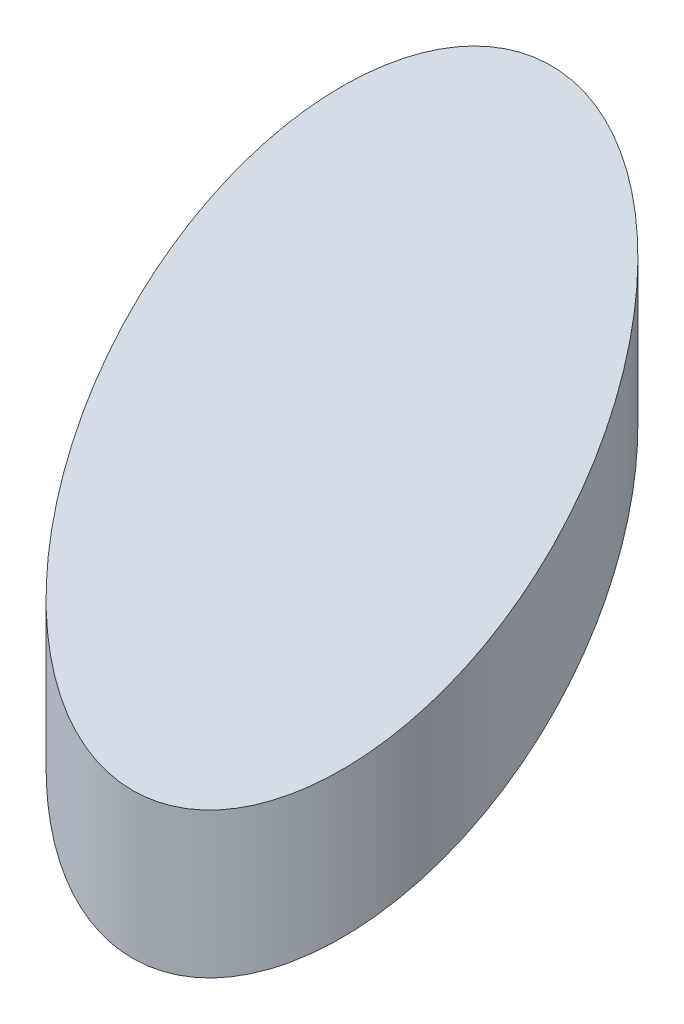
SolidWorks part; units mm, degrees
material "Glass"
ref_plane "Front Plane" through (0, 0, 0) normal (0, 0, 1) x (1, 0, 0)
ref_plane "Top Plane" through (0, 0, 0) normal (0, 1, 0) x (1, 0, 0)
ref_plane "Right Plane" through (0, 0, 0) normal (1, 0, 0) x (0, 0, -1)
sketch "Sketch2" plane through (0, 0, 0) normal (0, 1, 0) x (1, 0, 0)
  circle A0 centre (0, 0) radius 27.5
  dimension "D1" = 55
extrude "Boss-Extrude1" add sketch "Sketch2" along normal blind 80
sketch "Sketch3" plane through (0, 0, 0) normal (1, 0, 0) x (0, 0, -1)
  line L0 (27.5, 80) -> (-27.5, 80)
  line L1 (-27.5, 80) -> (-27.5, 19.11)
  line L2 (-27.5, 80) -> (-27.5, 0) construction
  line L3 (-27.5, 19.11) -> (27.5, 74.11)
  line L4 (27.5, 0) -> (27.5, 80) construction
  line L5 (27.5, 74.11) -> (27.5, 80)
  line L6 (27.5, 0) -> (27.5, 55)
  line L7 (27.5, 55) -> (-27.5, 0)
  line L8 (-27.5, 0) -> (27.5, 0)
  dimension "D1" = 45
  dimension "D2" = 13.5128
extrude "Cut-Extrude2" cut sketch "Sketch3" against normal through all both and the other way through all
